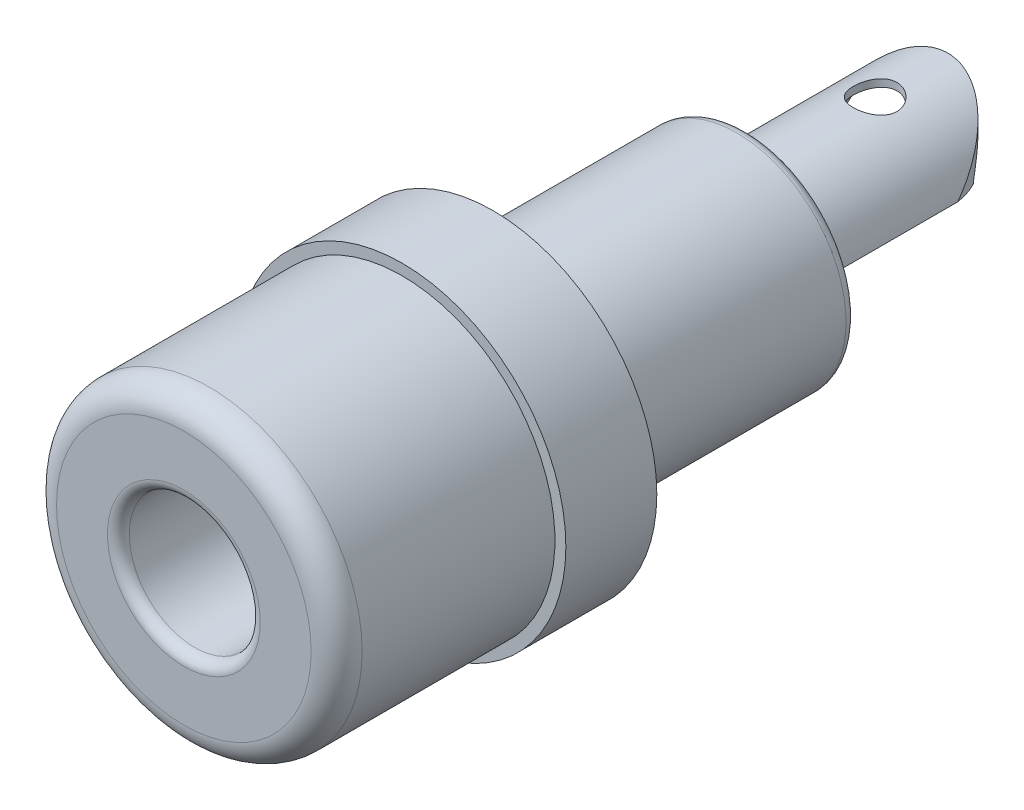
SolidWorks part; units mm, degrees
ref_plane "Спереди" through (0, 0, 0) normal (0, 0, 1) x (1, 0, 0)
ref_plane "Сверху" through (0, 0, 0) normal (0, 1, 0) x (1, 0, 0)
ref_plane "Справа" through (0, 0, 0) normal (1, 0, 0) x (0, 0, -1)
sketch "Эскиз1" plane through (0, 0, 0) normal (0, 0, 1) x (1, 0, 0)
  circle A0 centre (0, 0) radius 4.2
  circle A1 centre (0, 0) radius 1.8
  dimension "D1" = 8.4
  dimension "D2" = 3.6
extrude "Вытянуть1" add sketch "Эскиз1" along normal blind 6
sketch "Эскиз2" plane through (0, 0, 0) normal (0, 0, -1) x (-1, 0, 0)
  circle A0 centre (0, 0) radius 4.5
  circle A1 centre (0, 0) radius 1.8 construction
  circle A2 centre (0, 0) radius 1.8
  dimension "D1" = 9
extrude "Вытянуть2" add sketch "Эскиз2" along normal blind 2.5
sketch "Эскиз3" plane through (0, 0, -2.5) normal (0, 0, -1) x (-1, 0, 0)
  circle A0 centre (0, 0) radius 3
  circle A1 centre (0, 0) radius 1.8 construction
  circle A2 centre (0, 0) radius 1.8
  dimension "D1" = 6
extrude "Вытянуть3" add sketch "Эскиз3" along normal blind 7
sketch "Эскиз4" plane through (0, 0, -9.5) normal (0, 0, -1) x (-1, 0, 0)
  line L0 (-1.9774, 0.3) -> (-1.7748, 0.3)
  line L1 (1.7748, 0.3) -> (1.9774, 0.3)
  circle A0 centre (0, 0) radius 1.8 construction
  arc A1 (1.7748, 0.3) -> (-1.7748, 0.3) centre (0, 0) ccw
  arc A2 (1.9774, 0.3) -> (-1.9774, 0.3) centre (0, 0) ccw
  dimension "D1" = 4
  dimension "D2" = 0.3
extrude "Вытянуть4" add sketch "Эскиз4" along normal offset from surface (5.5 mm away) 21 up to face at (4.2, 0, 6)
sketch "Эскиз5" plane through (0, 0, 0) normal (0, 1, 0) x (1, 0, 0)
  line L0 (0, 0) -> (0, 16.8398) construction
  line L1 (1.9774, 15) -> (-1.9774, 15) construction
  line L2 (1.9993, 13.0007) -> (4.8609, 13.0007)
  line L3 (4.8609, 13.0007) -> (4.8609, 16.5985)
  line L4 (4.8609, 16.5985) -> (-4.3327, 16.5985)
  line L5 (-4.3327, 16.5985) -> (-4.3327, 13.0007)
  line L6 (-4.3327, 13.0007) -> (-1.9993, 13.0007)
  arc A0 (1.9993, 13.0007) -> (-1.9993, 13.0007) centre (0, 13.0007) ccw
  circle A1 centre (0, 13.0007) radius 0.6
  dimension "D1" = 1.2
extrude "Вырез-Вытянуть1" cut sketch "Эскиз5" along normal blind 21
fillet "Скругление1" radius 0.7 1 edges at (4.2, 0, 6)
fillet "Скругление2" radius 0.3 2 edges at (1.8, 0, 6) (-3, 0, -9.5)
